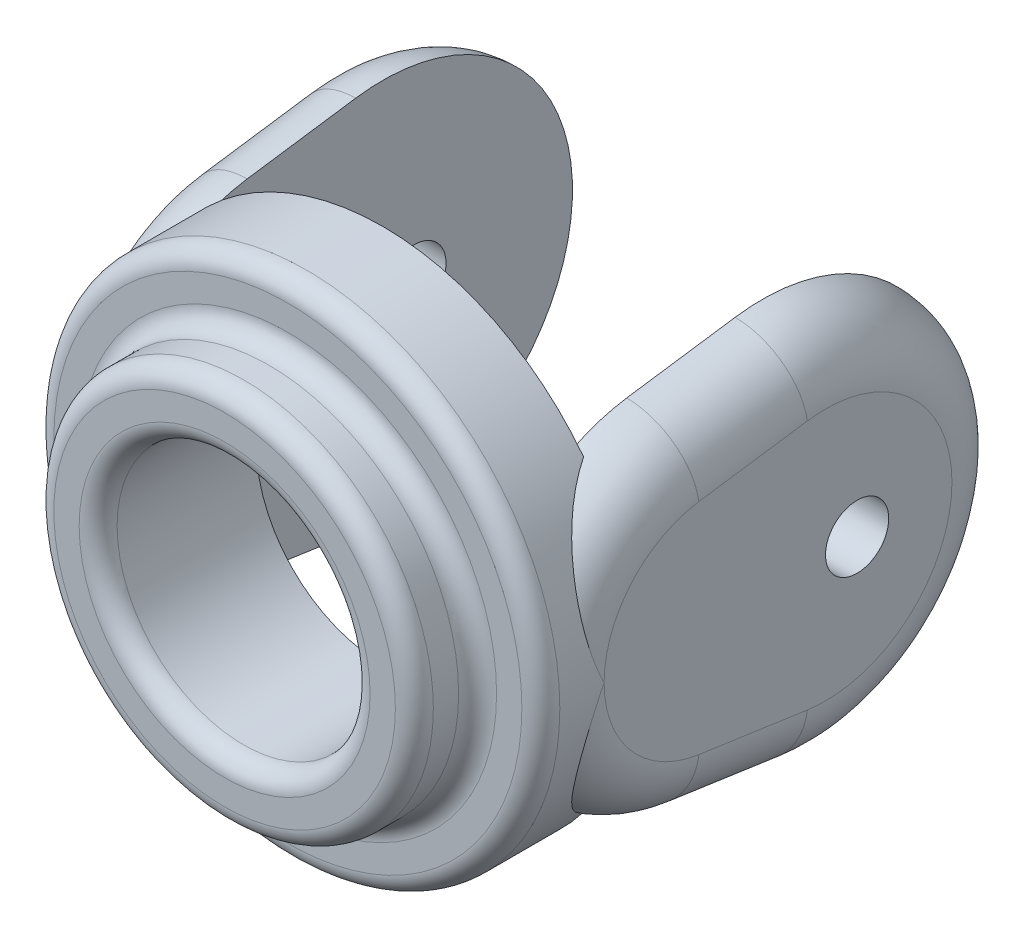
SolidWorks part; units mm, degrees
ref_plane "정면" through (0, 0, 0) normal (0, 0, 1) x (1, 0, 0)
ref_plane "윗면" through (0, 0, 0) normal (0, 1, 0) x (1, 0, 0)
ref_plane "우측면" through (0, 0, 0) normal (1, 0, 0) x (0, 0, -1)
sketch "스케치1" plane through (0, 0, 0) normal (0, 0, 1) x (1, 0, 0)
  circle A0 centre (0, 0) radius 40
extrude "보스-돌출1" add sketch "스케치1" along normal blind 10 and the other way blind 5
sketch "스케치2" plane through (0, 0, 10) normal (0, 0, 1) x (1, 0, 0)
  circle A0 centre (0, 0) radius 30
extrude "보스-돌출2" add sketch "스케치2" along normal blind 10
sketch "스케치3" plane through (0, 0, 20) normal (0, 0, 1) x (1, 0, 0)
  circle A0 centre (0, 0) radius 20
extrude "컷-돌출1" cut sketch "스케치3" against normal through all
ref_plane "평면1" through (40, 0, 0) normal (1, 0, 0) x (0, 0, -1)
sketch "스케치6" plane through (40, 0, 0) normal (1, 0, 0) x (0, 0, -1)
  line L0 (-10, 0) -> (65, 0) construction
  line L1 (-10, 40) -> (-10, -40) construction
  line L2 (13.5714, 27.2179) -> (30.7143, 29.6923)
  line L3 (13.5714, -27.2179) -> (30.7143, -29.6923)
  arc A0 (13.5714, 27.2179) -> (13.5714, -27.2179) centre (17.5, 0) ccw
  arc A1 (30.7143, -29.6923) -> (30.7143, 29.6923) centre (35, 0) ccw
extrude "보스-돌출3" add sketch "스케치6" against normal blind 10
ref_plane "평면2" through (-40, 0, 0) normal (1, 0, 0) x (0, 0, -1)
sketch "스케치7" plane through (-40, 0, 0) normal (1, 0, 0) x (0, 0, -1)
  line L0 (-10, 0) -> (65, 0) construction
  line L1 (-10, 30) -> (-10, -30) construction
  line L2 (30.7143, 29.6923) -> (13.5714, 27.2179)
  line L3 (30.7143, -29.6923) -> (13.5714, -27.2179)
  arc A0 (13.5714, 27.2179) -> (13.5714, -27.2179) centre (17.5, 0) ccw
  arc A1 (30.7143, -29.6923) -> (30.7143, 29.6923) centre (35, 0) ccw
extrude "보스-돌출4" add sketch "스케치7" along normal blind 10
sketch "스케치8" plane through (-40, 0, 0) normal (1, 0, 0) x (0, 0, -1)
  circle A0 centre (40, 0) radius 5
extrude "컷-돌출2" cut sketch "스케치8" against normal through all and the other way through all
fillet "필렛1" radius 10 13 edges at (30.8114, 24.4949, -5) (35, -27.2179, -13.5714) (37.0071, -15.1813, 5.4299) (30.8114, -24.4949, -5) (35, 29.6923, -30.7143) (35, -29.6923, -30.7143) (38.6857, 10.1692, 8.0507) (35, 27.2179, -13.5714) (40, 0, -65) (40, 28.4551, -22.1429) (40, 18.003, 3.288) (40, -18.003, 3.288) (40, -28.4551, -22.1429)
fillet "필렛2" radius 10 13 edges at (-37.0071, -15.1813, 5.4299) (-30.8114, 24.4949, -5) (-35, 27.2179, -13.5714) (-40, 18.003, 3.288) (-38.3918, -11.228, -42.6034) (-40, -18.003, 3.288) (-30.8114, -24.4949, -5) (-40, -28.4551, -22.1429) (-35, -27.2179, -13.5714) (-40, 0, -65) (-35, -29.6923, -30.7143) (-40, 28.4551, -22.1429) (-35, 29.6923, -30.7143)
fillet "필렛3" radius 3 2 edges at (40, 0, 10) (30, 0, 10)
fillet "필렛4" radius 3 2 edges at (30, 0, 20) (20, 0, 20)
